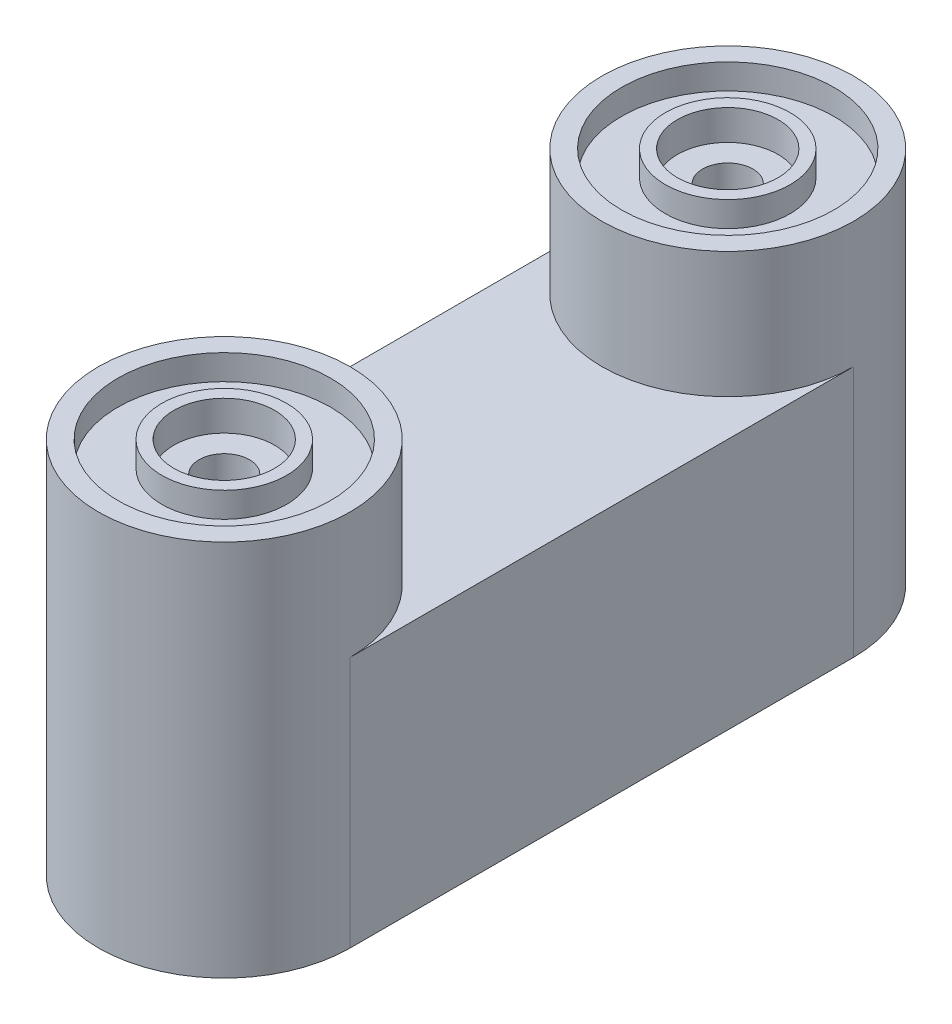
SolidWorks part; units mm, degrees
ref_plane "Ebene vorne" through (0, 0, 0) normal (0, 0, 1) x (1, 0, 0)
ref_plane "Ebene oben" through (0, 0, 0) normal (0, 1, 0) x (1, 0, 0)
ref_plane "Ebene rechts" through (0, 0, 0) normal (1, 0, 0) x (0, 0, -1)
sketch "Skizze1" plane through (0, 0, 0) normal (0, 0, 1) x (1, 0, 0)
  line L1 (-25, -25) -> (25, -25)
  line L2 (-25, -25) -> (-25, 25)
  line L3 (-25, 25) -> (25, 25)
  line L4 (25, -25) -> (25, 25)
  line L5 (-25, -25) -> (25, 25) construction
  line L6 (-25, 25) -> (25, -25) construction
  point P0 (0, 0)
  dimension "D1" = 50
  dimension "D2" = 50
extrude "Aufsatz-Linear austragen1" add sketch "Skizze1" along normal blind 150
sketch "Skizze2" plane through (0, 25, 0) normal (0, 1, 0) x (1, 0, 0)
  line L0 (25, -150) -> (25, 0) construction
  line L1 (-25, -150) -> (25, -150)
  line L2 (-25, -150) -> (-25, -100)
  line L3 (-25, -100) -> (25, -100)
  line L4 (25, -150) -> (25, -100)
  line L6 (-25, 0) -> (25, 0)
  line L7 (-25, 0) -> (-25, -50)
  line L8 (-25, -50) -> (25, -50)
  line L9 (25, 0) -> (25, -50)
  dimension "D1" = 50
  dimension "D2" = 50
extrude "Aufsatz-Linear austragen2" add sketch "Skizze2" along normal blind 25
sketch "Skizze3" plane through (0, 50, 0) normal (0, 1, 0) x (1, 0, 0)
  line L0 (-25, 0) -> (25, 0)
  line L1 (25, 0) -> (25, -50)
  line L2 (25, -50) -> (-25, -50)
  line L3 (-25, -50) -> (-25, 0)
  line L4 (-25, -100) -> (25, -100)
  line L5 (25, -100) -> (25, -150)
  line L6 (25, -150) -> (-25, -150)
  line L7 (-25, -150) -> (-25, -100)
  circle A0 centre (0, -25) radius 25
  circle A1 centre (0, -125) radius 25
  line M2 (-25, 0) -> (-25, -50)
  line M3 (-25, -50) -> (25, -50)
  line M4 (25, -50) -> (25, 0)
  line M5 (25, 0) -> (-25, 0)
extrude "Schnitt-Linear austragen1" cut sketch "Skizze3" against normal blind 25 contours A0 L0 M2 | A0 L1 M5 | A1 L6 L5 | A1 L7 L6 | A1 L4 L7 | A1 L5 L4 | A0 L3 M3 | A0 L2 M4 region at (-19.4158, 50, 5.5842) region at (19.4158, 50, 5.5842) region at (-19.4158, 50, 44.4158) region at (19.4158, 50, 44.4158) region at (-19.4158, 50, 105.5842) region at (19.4158, 50, 105.5842) region at (-19.4158, 50, 144.4158) region at (19.4158, 50, 144.4158)
sketch "Skizze4" plane through (0, 25, 0) normal (0, 1, 0) x (1, 0, 0)
  line L0 (-25, -25) -> (-25, 0)
  line L1 (-25, 0) -> (25, 0)
  line L2 (25, 0) -> (25, -25)
  line L3 (25, -25) -> (25, -125)
  line L4 (25, -125) -> (25, -150)
  line L5 (25, -150) -> (-25, -150)
  line L6 (-25, -150) -> (-25, -125)
  circle A0 centre (0, -25) radius 25
  circle A1 centre (0, -125) radius 25
  arc M1 (-25, -25) -> (0, 0) centre (0, -25) cw
  line M2 (0, 0) -> (-25, 0)
  line M3 (-25, 0) -> (-25, -25)
extrude "Schnitt-Linear austragen2" cut sketch "Skizze4" against normal blind 50 contours A1 L6 L5 | A1 L5 L4 | M3 M1 M2 | A0 L2 L1 region at (19.4158, 25, 144.4158) region at (-19.4158, 25, 5.5842) region at (19.4158, 25, 5.5842) region at (-19.4158, 25, 144.4158)
sketch "Skizze5" plane through (0, 50, 0) normal (0, 1, 0) x (1, 0, 0)
  circle A0 centre (0, -25) radius 5
  circle A1 centre (0, -125) radius 5
extrude "Schnitt-Linear austragen3" cut sketch "Skizze5" against normal blind 75
sketch "Skizze6" plane through (0, 50, 0) normal (0, 1, 0) x (1, 0, 0)
  circle A0 centre (0, -125) radius 10
  circle A1 centre (0, -25) radius 10
extrude "Schnitt-Linear austragen4" cut sketch "Skizze6" against normal blind 6
sketch "Skizze7" plane through (0, -25, 0) normal (0, -1, 0) x (1, 0, 0)
  circle A0 centre (0, 125) radius 10
  circle A1 centre (0, 25) radius 10
extrude "Schnitt-Linear austragen5" cut sketch "Skizze7" against normal blind 6
sketch "Skizze8" plane through (0, 50, 0) normal (0, 1, 0) x (1, 0, 0)
  line L0 (0, -25) -> (0, -125) construction
  line L1 (0, -75) -> (13.0656, -75) construction
  circle A0 centre (0, -25) radius 21.1
  circle A1 centre (0, -25) radius 12.4
  circle A2 centre (0, -125) radius 12.4
  circle A3 centre (0, -125) radius 21.1
  dimension "D1" = 24.8
  dimension "D2" = 42.2
extrude "Schnitt-Linear austragen6" cut sketch "Skizze8" against normal blind 5
